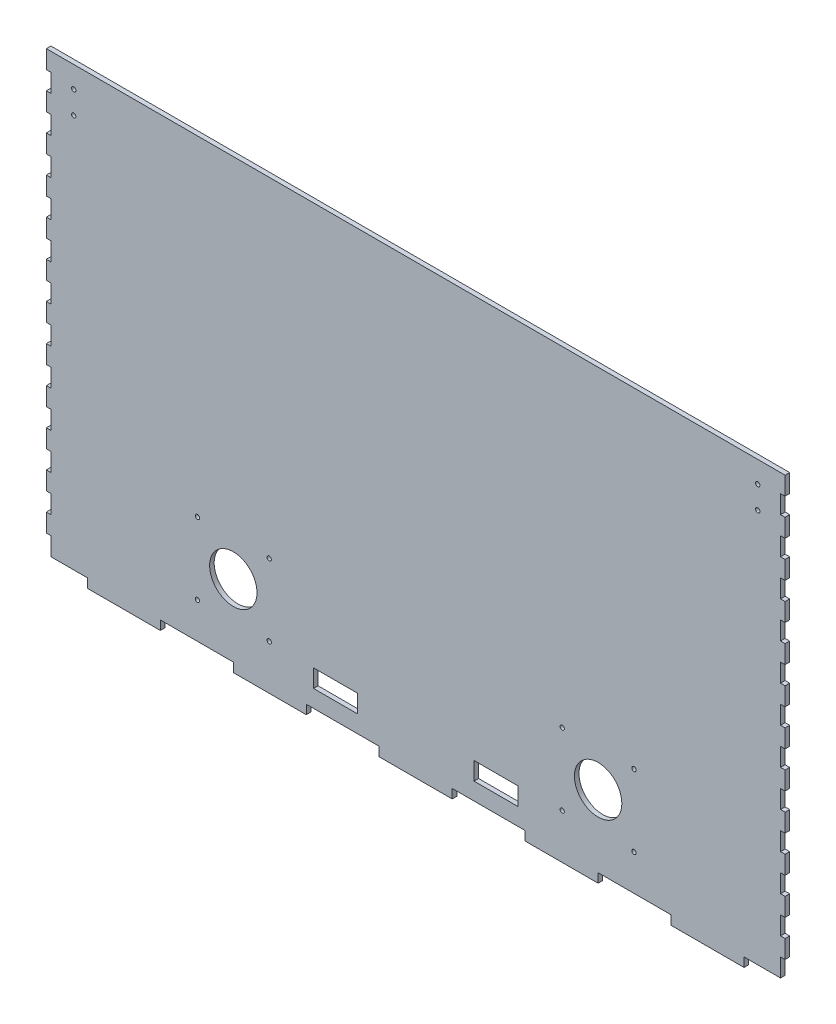
SolidWorks part; units mm, degrees
ref_plane "Front Plane" through (0, 0, 0) normal (0, 0, 1) x (1, 0, 0)
ref_plane "Top Plane" through (0, 0, 0) normal (0, 1, 0) x (1, 0, 0)
ref_plane "Right Plane" through (0, 0, 0) normal (1, 0, 0) x (0, 0, -1)
sketch "Sketch1" plane through (0, 0, 0) normal (0, 0, 1) x (1, 0, 0)
  line L0 (0, 0) -> (508, 0)
  line L1 (508, 0) -> (508, 304.8)
  line L2 (508, 304.8) -> (0, 304.8)
  line L3 (0, 304.8) -> (0, 0)
  line L4 (254, 304.8) -> (254, 0) construction
  line L5 (0, 304.8) -> (-3.175, 304.8)
  line L6 (-3.175, 304.8) -> (-3.175, 292.1)
  line L7 (-3.175, 292.1) -> (0, 292.1)
  line L8 (25.4, 0) -> (25.4, -6.35)
  line L9 (25.4, -6.35) -> (76.2, -6.35)
  line L10 (76.2, -6.35) -> (76.2, 0)
  line L13 (0, 279.4) -> (-3.175, 279.4)
  line L14 (-3.175, 279.4) -> (-3.175, 266.7)
  line L15 (-3.175, 266.7) -> (0, 266.7)
  line L17 (0, 254) -> (-3.175, 254)
  line L18 (-3.175, 254) -> (-3.175, 241.3)
  line L19 (-3.175, 241.3) -> (0, 241.3)
  line L21 (0, 228.6) -> (-3.175, 228.6)
  line L22 (-3.175, 228.6) -> (-3.175, 215.9)
  line L23 (-3.175, 215.9) -> (0, 215.9)
  line L25 (0, 203.2) -> (-3.175, 203.2)
  line L26 (-3.175, 203.2) -> (-3.175, 190.5)
  line L27 (-3.175, 190.5) -> (0, 190.5)
  line L29 (0, 177.8) -> (-3.175, 177.8)
  line L30 (-3.175, 177.8) -> (-3.175, 165.1)
  line L31 (-3.175, 165.1) -> (0, 165.1)
  line L33 (0, 152.4) -> (-3.175, 152.4)
  line L34 (-3.175, 152.4) -> (-3.175, 139.7)
  line L35 (-3.175, 139.7) -> (0, 139.7)
  line L37 (0, 127) -> (-3.175, 127)
  line L38 (-3.175, 127) -> (-3.175, 114.3)
  line L39 (-3.175, 114.3) -> (0, 114.3)
  line L41 (0, 101.6) -> (-3.175, 101.6)
  line L42 (-3.175, 101.6) -> (-3.175, 88.9)
  line L43 (-3.175, 88.9) -> (0, 88.9)
  line L45 (0, 76.2) -> (-3.175, 76.2)
  line L46 (-3.175, 76.2) -> (-3.175, 63.5)
  line L47 (-3.175, 63.5) -> (0, 63.5)
  line L49 (0, 50.8) -> (-3.175, 50.8)
  line L50 (-3.175, 50.8) -> (-3.175, 38.1)
  line L51 (-3.175, 38.1) -> (0, 38.1)
  line L53 (0, 25.4) -> (-3.175, 25.4)
  line L54 (-3.175, 25.4) -> (-3.175, 12.7)
  line L55 (-3.175, 12.7) -> (0, 12.7)
  line L57 (0, 304.8) -> (0, 279.4) construction
  line L59 (127, 0) -> (127, -6.35)
  line L60 (127, -6.35) -> (177.8, -6.35)
  line L61 (177.8, -6.35) -> (177.8, 0)
  line L63 (228.6, 0) -> (228.6, -6.35)
  line L64 (228.6, -6.35) -> (279.4, -6.35)
  line L65 (279.4, -6.35) -> (279.4, 0)
  line L67 (330.2, 0) -> (330.2, -6.35)
  line L68 (330.2, -6.35) -> (381, -6.35)
  line L69 (381, -6.35) -> (381, 0)
  line L70 (76.2, 0) -> (177.8, 0) construction
  line L72 (431.8, 0) -> (431.8, -6.35)
  line L73 (431.8, -6.35) -> (482.6, -6.35)
  line L74 (482.6, -6.35) -> (482.6, 0)
  line L76 (511.175, 12.7) -> (508, 12.7)
  line L77 (511.175, 25.4) -> (511.175, 12.7)
  line L78 (508, 25.4) -> (511.175, 25.4)
  line L80 (511.175, 38.1) -> (508, 38.1)
  line L81 (511.175, 50.8) -> (511.175, 38.1)
  line L82 (508, 50.8) -> (511.175, 50.8)
  line L84 (511.175, 63.5) -> (508, 63.5)
  line L85 (511.175, 76.2) -> (511.175, 63.5)
  line L86 (508, 76.2) -> (511.175, 76.2)
  line L88 (511.175, 88.9) -> (508, 88.9)
  line L89 (511.175, 101.6) -> (511.175, 88.9)
  line L90 (508, 101.6) -> (511.175, 101.6)
  line L92 (511.175, 114.3) -> (508, 114.3)
  line L93 (511.175, 127) -> (511.175, 114.3)
  line L94 (508, 127) -> (511.175, 127)
  line L96 (511.175, 139.7) -> (508, 139.7)
  line L97 (511.175, 152.4) -> (511.175, 139.7)
  line L98 (508, 152.4) -> (511.175, 152.4)
  line L100 (511.175, 165.1) -> (508, 165.1)
  line L101 (511.175, 177.8) -> (511.175, 165.1)
  line L102 (508, 177.8) -> (511.175, 177.8)
  line L104 (511.175, 190.5) -> (508, 190.5)
  line L105 (511.175, 203.2) -> (511.175, 190.5)
  line L106 (508, 203.2) -> (511.175, 203.2)
  line L108 (511.175, 215.9) -> (508, 215.9)
  line L109 (511.175, 228.6) -> (511.175, 215.9)
  line L110 (508, 228.6) -> (511.175, 228.6)
  line L112 (511.175, 241.3) -> (508, 241.3)
  line L113 (511.175, 254) -> (511.175, 241.3)
  line L114 (508, 254) -> (511.175, 254)
  line L116 (511.175, 266.7) -> (508, 266.7)
  line L117 (511.175, 279.4) -> (511.175, 266.7)
  line L118 (508, 279.4) -> (511.175, 279.4)
  line L120 (511.175, 292.1) -> (508, 292.1)
  line L121 (511.175, 304.8) -> (511.175, 292.1)
  line L122 (508, 304.8) -> (511.175, 304.8)
  dimension "D1" = 508
  dimension "D2" = 304.8
  dimension "D3" = 3.175
  dimension "D4" = 12.7
  dimension "D5" = 6.35
  dimension "D6" = 50.8
  dimension "D7" = 25.4
  dimension "D9" = 25.4
  dimension "D11" = 101.6
  dimension "D8" = 12
  dimension "D10" = 5
extrude "Boss-Extrude1" add sketch "Sketch1" along normal blind 3.175 contours L2 L3 L0 L1 | L9 L10 L0 L8 | L60 L61 L0 L59 | L64 L65 L0 L63 | L68 L69 L0 L67 | L73 L74 L0 L72 | L54 L55 L3 L53 | L50 L51 L3 L49 | L46 L47 L3 L45 | L42 L43 L3 L41 | L38 L39 L3 L37 | L34 L35 L3 L33 | L30 L31 L3 L29 | L26 L27 L3 L25 | L22 L23 L3 L21 | L18 L19 L3 L17 | L14 L15 L3 L13 | L6 L7 L3 L5 | L78 L1 L76 L77 | L82 L1 L80 L81 | L86 L1 L84 L85 | L90 L1 L88 L89 | L98 L1 L96 L97 | L94 L1 L92 L93 | L102 L1 L100 L101 | L106 L1 L104 L105 | L110 L1 L108 L109 | L114 L1 L112 L113 | L118 L1 L116 L117 | L122 L1 L120 L121 region at (254, 152.4, 0) region at (50.8, -3.175, 0) region at (-1.5875, 19.05, 0) region at (152.4, -3.175, 0) region at (-1.5875, 44.45, 0) region at (254, -3.175, 0) region at (-1.5875, 69.85, 0) region at (355.6, -3.175, 0) region at (-1.5875, 95.25, 0) region at (457.2, -3.175, 0) region at (-1.5875, 120.65, 0) region at (-1.5875, 146.05, 0) region at (509.5875, 19.05, 0) region at (-1.5875, 171.45, 0) region at (509.5875, 44.45, 0) region at (-1.5875, 196.85, 0) region at (509.5875, 69.85, 0) region at (-1.5875, 222.25, 0) region at (509.5875, 95.25, 0) region at (-1.5875, 247.65, 0) region at (509.5875, 120.65, 0) region at (-1.5875, 273.05, 0) region at (509.5875, 146.05, 0) region at (-1.5875, 298.45, 0) region at (509.5875, 171.45, 0) region at (509.5875, 298.45, 0) region at (509.5875, 196.85, 0) region at (509.5875, 273.05, 0) region at (509.5875, 222.25, 0) region at (509.5875, 247.65, 0)
sketch "Sketch2" plane through (0, 0, 3.175) normal (0, 0, 1) x (1, 0, 0)
  line L0 (254, 304.8) -> (254, -6.35) construction
  line L1 (511.175, 304.8) -> (-3.175, 304.8) construction
  line L2 (228.6, -6.35) -> (279.4, -6.35) construction
  line L3 (0, 6.35) -> (254, 6.35) construction
  line L5 (0, 12.7) -> (0, 0) construction
  line L6 (127, 6.35) -> (127, 304.8) construction
  line L7 (110.5, 50) -> (143.5, 50) construction
  line L8 (76.2, 0) -> (127, 0) construction
  circle A0 centre (127, 50) radius 16.5
  circle A1 centre (102, 75) radius 1.5
  circle A2 centre (152, 75) radius 1.5
  circle A3 centre (152, 25) radius 1.5
  circle A4 centre (102, 25) radius 1.5
  circle A5 centre (381, 50) radius 16.5
  circle A6 centre (356, 75) radius 1.5
  circle A7 centre (356, 25) radius 1.5
  circle A8 centre (406, 25) radius 1.5
  circle A9 centre (406, 75) radius 1.5
  dimension "D1" = 33
  dimension "D2" = 3
  dimension "D3" = 25
  dimension "D4" = 25
  dimension "D5" = 50
extrude "Cut-Extrude1" cut sketch "Sketch2" against normal up to surface (3.175 mm away) up to face at (254, 125.5767, 0)
sketch "Sketch3" plane through (0, 0, 3.175) normal (0, 0, 1) x (1, 0, 0)
  line L1 (511.175, 304.8) -> (-3.175, 304.8) construction
  line L2 (254, 304.8) -> (254, -6.35) construction
  line L3 (228.6, -6.35) -> (279.4, -6.35) construction
  line L4 (-3.175, 304.8) -> (-3.175, 292.1) construction
  circle A0 centre (15.875, 289.8) radius 1.5
  circle A1 centre (15.875, 274.05) radius 1.5
  circle A2 centre (492.125, 289.8) radius 1.5
  circle A3 centre (492.125, 274.05) radius 1.5
  dimension "D1" = 3
  dimension "D2" = 3
  dimension "D3" = 19.05
  dimension "D4" = 15.75
  dimension "D5" = 15
extrude "Cut-Extrude2" cut sketch "Sketch3" against normal up to surface (3.175 mm away) up to face at (103.5, 75, 0)
sketch "Sketch4" plane through (0, 0, 3.175) normal (0, 0, 1) x (1, 0, 0)
  line L0 (254, 304.8) -> (254, -6.35) construction
  line L1 (511.175, 304.8) -> (-3.175, 304.8) construction
  line L2 (228.6, -6.35) -> (279.4, -6.35) construction
  line L3 (182.8125, 12.011) -> (213.3875, 12.011)
  line L4 (213.3875, 12.011) -> (213.3875, 24.45)
  line L5 (213.3875, 24.45) -> (182.8125, 24.45)
  line L6 (182.8125, 24.45) -> (182.8125, 12.011)
  line L7 (-3.175, 25.4) -> (-3.175, 12.7) construction
  line L8 (177.8, 0) -> (228.6, 0) construction
  line L9 (325.1875, 24.45) -> (325.1875, 12.011)
  line L10 (294.6125, 24.45) -> (325.1875, 24.45)
  line L11 (294.6125, 12.011) -> (294.6125, 24.45)
  line L12 (325.1875, 12.011) -> (294.6125, 12.011)
  dimension "D1" = 185.9875
  dimension "D2" = 24.45
  dimension "D3" = 12.439
  dimension "D4" = 30.575
extrude "Interactable Hole Cut" cut sketch "Sketch4" against normal up to surface (3.175 mm away) up to face at (17.375, 274.05, 0)
equation "\"wall_thickness\"= 0.125in"
equation "\"base_thickness\"= 0.25in"
equation "\"D3@Sketch1\"=\"wall_thickness\""
equation "\"D5@Sketch1\"=\"base_thickness\""
equation "\"D1@Boss-Extrude1\"=\"wall_thickness\""
